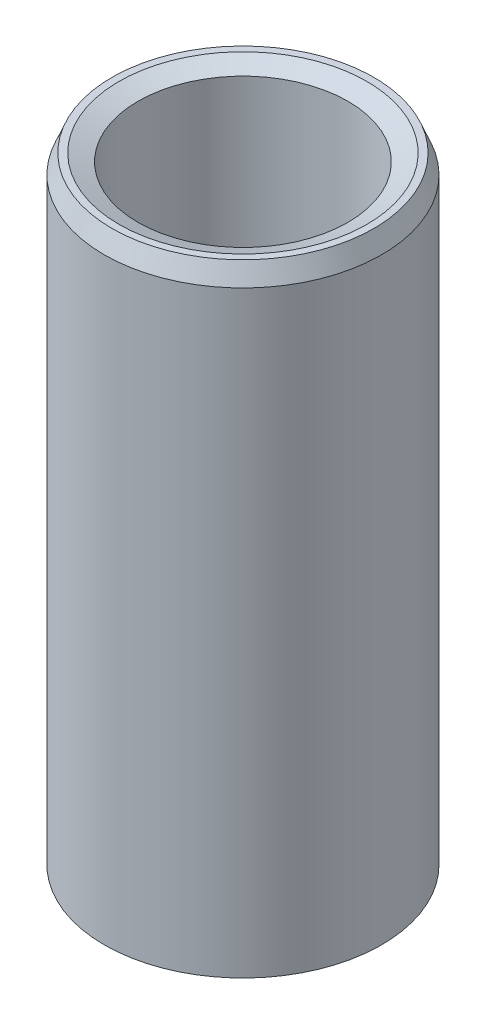
SolidWorks part; units mm, degrees
ref_plane "Front Plane" through (0, 0, 0) normal (0, 0, 1) x (1, 0, 0)
ref_plane "Top Plane" through (0, 0, 0) normal (0, 1, 0) x (1, 0, 0)
ref_plane "Right Plane" through (0, 0, 0) normal (1, 0, 0) x (0, 0, -1)
sketch "Sketch1" plane through (0, 0, 0) normal (0, 1, 0) x (1, 0, 0)
  circle A0 centre (0, 0) radius 17.5
  dimension "SLEEVE_OD" = 35
extrude "Boss-Extrude1" add sketch "Sketch1" along normal blind 78.797
sketch "Sketch2" plane through (0, 0, 0) normal (0, 1, 0) x (1, 0, 0)
  circle A0 centre (0, 0) radius 13.2473
  dimension "BORE_D" = 26.4947
extrude "Cut-Extrude1" cut sketch "Sketch2" along normal through all
chamfer "Chamfer1" distance 2.3915 angle 22.137 4 edges at (0, 78.797, 13.2473) (0, 0, 13.2473) (0, 0, 17.5) (0, 78.797, 17.5) first distance on face at (0, 78.797, 13.2473) first distance on face at (0, 0, 13.2473) first distance on face at (0, 78.797, 17.5)
